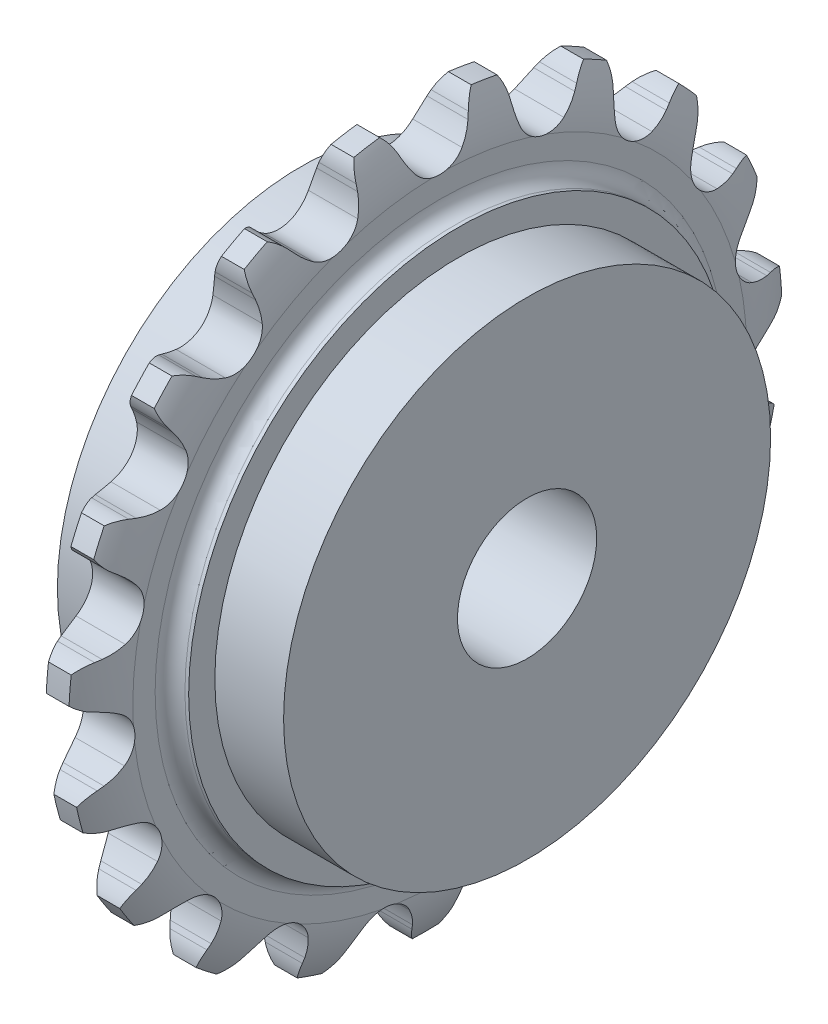
SolidWorks part; units mm, degrees
material "AISI 1020"
ref_plane "Front" through (0, 0, 0) normal (0, 0, 1) x (1, 0, 0)
ref_plane "Top" through (0, 0, 0) normal (0, 1, 0) x (1, 0, 0)
ref_plane "Right" through (0, 0, 0) normal (1, 0, 0) x (0, 0, -1)
sketch "Sketch1" plane through (0, 0, 0) normal (0, 0, 1) x (1, 0, 0)
  line L0 (-4, 0) -> (4, 0) construction
  line L1 (-2.5486, 0) -> (-2.5486, 15.5)
  line L2 (-2.5486, 15.5) -> (-2.3346, 15.5)
  line L3 (-1.4787, 16.3559) -> (-1.4787, 17.6398)
  line L4 (-0.6532, 20.5) -> (0.6532, 20.5)
  line L5 (1.4787, 17.6398) -> (1.4787, 16.3559)
  line L6 (2.3346, 15.5) -> (2.5486, 15.5)
  line L7 (2.5486, 15.5) -> (2.5486, 0)
  line L8 (2.5486, 0) -> (-2.5486, 0)
  line L9 (0, 0) -> (0, 20.5) construction
  line L10 (-1.184, 19.2898) -> (1.184, 19.2898) construction
  line L11 (-1.184, -19.2898) -> (1.184, -19.2898) construction
  line L13 (-1.4787, 17.6398) -> (3.7984, 17.6398) construction
  line L14 (-1.4787, -17.6398) -> (3.7984, -17.6398) construction
  arc A0 (-0.6532, 20.5) -> (-1.4787, 17.6398) centre (4.865, 17.3581) ccw
  arc A1 (0.6532, 20.5) -> (1.4787, 17.6398) centre (-4.865, 17.3581) cw
  arc A2 (1.4787, 16.3559) -> (2.3346, 15.5) centre (2.3346, 16.3559) ccw
  arc A3 (-2.3346, 15.5) -> (-1.4787, 16.3559) centre (-2.3346, 16.3559) ccw
  point P30 (1.4787, 15.5)
  point P33 (-1.4787, 15.5)
  point P34 (24, 26.331)
  point P36 (27.3, 26.331)
  point P37 (24, 21.8279)
  point P38 (30, 21.8279)
  point P39 (24, 17.1531)
  point P40 (27.18, 17.1531)
  point P41 (24, 13.3224)
  point P42 (30.4, 13.3224)
  point P43 (24, 30.8002)
  point P44 (43, 30.8002)
  point P45 (24, 35.1098)
  point P46 (30.35, 35.1098)
  dimension "D1" = 2.1398
  dimension "rx" = 6.35
  dimension "D3" = 0.8559
  dimension "d" = 38.5796
  dimension "p" = 6.35
  dimension "z" = 19
  dimension "da" = 41
  dimension "df" = 35.2796
  dimension "dr" = 3.3
  dimension "dg" = 31
  dimension "h" = 6
  dimension "bf1" = 2.9574
  dimension "b1" = 3.18
  dimension "ba" = 0.8255
  dimension "D2" = 1.0699
  dimension "pt" = 6.4
revolve "Revolve" add sketch "Sketch1" angle 360 about L0
ref_axis "Axis1" through (-8.5448, 0, 0) along (1, 0, 0)
sketch "Sketch2" plane through (0, 0, 0) normal (1, 0, 0) x (0, 0, -1)
  line L0 (0, 0) -> (0, 20.5) construction
  line L1 (0, 0) -> (-3.3742, 20.2204) construction
  line L2 (0, 0) -> (-6.6563, 19.3893) construction
  line L3 (1.3432, 18.2344) -> (-6.1833, 24.1482) construction
  line L4 (1.9236, 19.2145) -> (-2.0759, 20.9209) construction
  line L5 (0, 0) -> (3.3742, 20.2204) construction
  line L6 (1.9236, 19.2145) -> (2.0513, 19.5139)
  line L7 (-1.9236, 19.2145) -> (-2.0513, 19.5139)
  circle A0 centre (0, 0) radius 20.5 construction
  arc A1 (1.3432, 18.2344) -> (-1.3432, 18.2344) centre (0, 19.2898) cw
  arc A2 (1.3432, 18.2344) -> (1.9236, 19.2145) centre (-2.0759, 20.9209) ccw
  arc A3 (2.6294, 20.3307) -> (2.0513, 19.5139) centre (4.2315, 18.5837) ccw
  arc A4 (-1.3432, 18.2344) -> (-1.9236, 19.2145) centre (2.0759, 20.9209) cw
  arc A5 (-2.6294, 20.3307) -> (-2.0513, 19.5139) centre (-4.2315, 18.5837) cw
  arc A7 (2.6294, 20.3307) -> (-2.6294, 20.3307) centre (0, 0) ccw
  dimension "r1" = 1.7083
  dimension "r3" = 2.3703
  dimension "D1" = 18.947
  dimension "D2" = 9.474
  dimension "av2" = 51.842
  dimension "M" = 2.0759
  dimension "T" = 1.6311
  dimension "beta" = 15.053
  dimension "yv2" = 13.632
  dimension "bc" = 0.3254
extrude "ExtrudeCutOne" cut sketch "Sketch2" against normal mid plane 5.0972
pattern_circular "PatternOne" count 19 over 360 about axis through (-4, 0, 0) along (1, 0, 0) of "ExtrudeCutOne"
sketch "SketchHole" plane through (0, 0, 0) normal (1, 0, 0) x (0, 0, -1)
  circle A0 centre (0, 0) radius 13.995
extrude "Cut-ExtrudeA" cut sketch "SketchHole" against normal through all and the other way through all
sketch "SketchKey" plane through (0, 0, 0) normal (1, 0, 0) x (0, 0, -1)
  line L1 (-4, 6.9975) -> (4, 6.9975)
  line L2 (-4, 6.9975) -> (-4, 17.295)
  line L3 (-4, 17.295) -> (4, 17.295)
  line L4 (4, 6.9975) -> (4, 17.295)
sketch "草图1" plane through (-2.5486, 0, 0) normal (-1, 0, 0) x (0, 0, 1)
  circle A0 centre (0, 0) radius 13.995
  circle A1 centre (0, 0) radius 4
  dimension "D1" = 8
extrude "凸台-拉伸1" add sketch "草图1" along normal mid plane 13 from surface starting at plane "Right"
